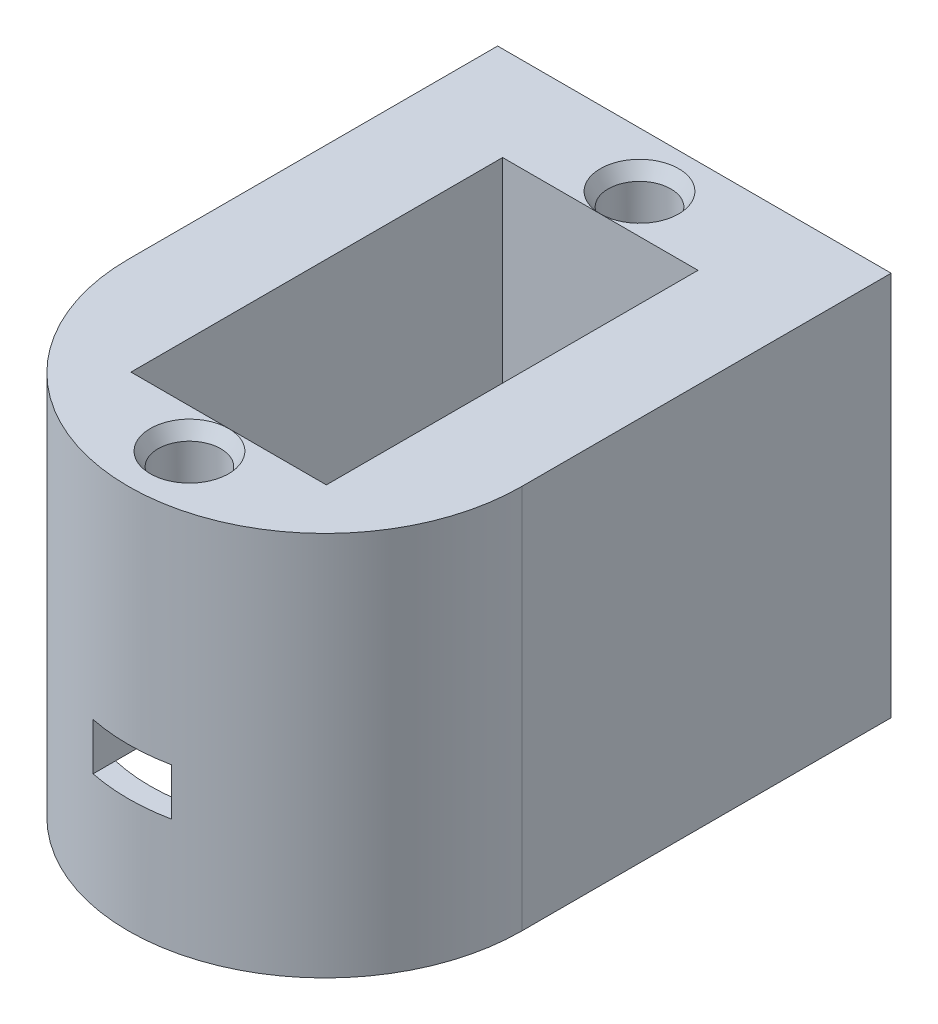
SolidWorks part; units mm, degrees
ref_plane "Front Plane" through (0, 0, 0) normal (0, 0, 1) x (1, 0, 0)
ref_plane "Top Plane" through (0, 0, 0) normal (0, 1, 0) x (1, 0, 0)
ref_plane "Right Plane" through (0, 0, 0) normal (1, 0, 0) x (0, 0, -1)
sketch "Sketch4" plane through (0, 0, 0) normal (0, 0, 1) x (1, 0, 0)
  line L1 (-6.23, 55.25) -> (6.23, 55.25)
  line L2 (-6.23, 55.25) -> (-6.23, 72.5)
  line L3 (-6.23, 72.5) -> (6.23, 72.5)
  line L4 (6.23, 55.25) -> (6.23, 72.5)
  point P4 (0, 72.5)
  dimension "D1" = 12.46
  dimension "D2" = 17.25
extrude "Boss-Extrude3" add sketch "Sketch4" along normal blind 6
sketch "Sketch8" plane through (0, 55.25, 0) normal (0, -1, 0) x (-1, 0, 0)
  circle A0 centre (0, -23.55) radius 12.5468
  circle A1 centre (0, -23.55) radius 11.15
  dimension "D1" = 22.3
  dimension "D2" = 23.55
extrude "Boss-Extrude6" add sketch "Sketch8" along normal blind 7.3 and the other way up to surface (17.25 mm away) other way up to face at (0, 72.5, 3)
sketch "Sketch5" plane through (0, 72.5, 0) normal (0, 1, 0) x (1, 0, 0)
  line L8 (12.5468, -23.55) -> (12.5468, 0)
  line L9 (12.5468, 0) -> (6.23, 0)
  line L10 (-12.5468, -23.55) -> (-12.5468, 0)
  line L11 (-12.5468, 0) -> (-6.23, 0)
  line L12 (-6.23, 0) -> (-6.23, -29.7)
  line L14 (6.23, -29.7) -> (6.23, 0)
  line L15 (-6.23, -29.7) -> (6.23, -29.7)
  line L16 (6.23, -6) -> (-6.23, -6) construction
  circle A0 centre (0, -23.55) radius 12.5468 construction
  arc A1 (-12.5468, -23.55) -> (12.5468, -23.55) centre (0, -23.55) ccw
  dimension "D1" = 23.7
  dimension "D2" = 23.55
extrude "Boss-Extrude4" add sketch "Sketch5" against normal up to surface (17.25 mm away) up to face at (0, 55.25, 3)
sketch "Sketch6" plane through (0, 72.5, 0) normal (0, 1, 0) x (1, 0, 0)
  line L0 (6.23, -6) -> (-6.23, -6) construction
  line L3 (6.23, -29.7) -> (-6.23, -29.7) construction
  circle A0 centre (0, -3.5) radius 2
  circle A1 centre (0, -32.2) radius 2
  dimension "D1" = 4
  dimension "D3" = 4
  dimension "D2" = 2.5
  dimension "D4" = 2.5
extrude "Cut-Extrude1" cut sketch "Sketch6" against normal blind 5
chamfer "Chamfer1" distance 0.5 angle 60 2 edges at (0, 72.5, 5.5) (0, 72.5, 34.2) first distance on face at (0, 72.5, 5.5)
sketch "Sketch10" plane through (0, 72.5, 0) normal (0, 1, 0) x (1, 0, 0)
  line L1 (-6.23, -6) -> (6.23, -6)
  line L2 (-6.23, -6) -> (-6.23, -29.7)
  line L3 (-6.23, -29.7) -> (6.23, -29.7)
  line L4 (6.23, -6) -> (6.23, -29.7)
extrude "Cut-Extrude3" cut sketch "Sketch10" against normal up to surface (17.25 mm away) up to face at (0, 55.25, 10.3399)
ref_plane "Plane1" through (0, 0, 36.0968) normal (0, 0, 1) x (1, 0, 0)
sketch "Sketch11" plane through (0, 0, 36.0968) normal (0, 0, 1) x (1, 0, 0)
  line L0 (-11.15, 55.25) -> (11.15, 55.25) construction
  line L1 (-2.5, 58.25) -> (2.5, 58.25)
  line L2 (-2.5, 58.25) -> (-2.5, 55.25)
  line L3 (-2.5, 55.25) -> (2.5, 55.25)
  line L4 (2.5, 58.25) -> (2.5, 55.25)
  point P4 (0, 58.25)
  dimension "D1" = 0
  dimension "D2" = 5
  dimension "D3" = 3
extrude "Cut-Extrude4" cut sketch "Sketch11" against normal up to next
sketch "Sketch13" plane through (0, 47.95, 0) normal (0, -1, 0) x (1, 0, 0)
  line L0 (-12.5468, 23.55) -> (-12.5468, 0)
  line L1 (-12.5468, 0) -> (12.5468, 0)
  line L2 (12.5468, 0) -> (12.5468, 23.55)
  arc A0 (-12.5468, 23.55) -> (12.5468, 23.55) centre (0, 23.55) ccw
extrude "Boss-Extrude7" add sketch "Sketch13" against normal up to surface (7.3 mm away) up to face at (0, 55.25, 10.3399)
